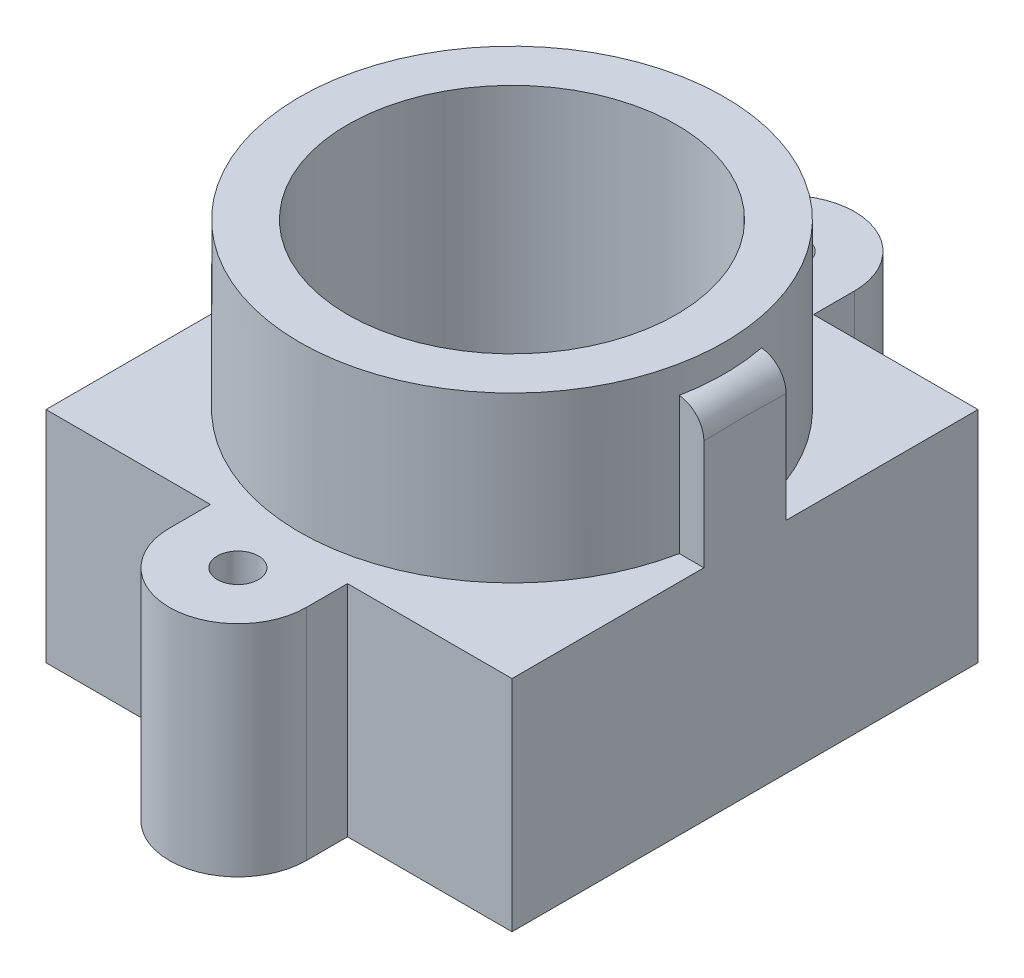
SolidWorks part; units mm, degrees
ref_plane "Front Plane" through (0, 0, 0) normal (0, 0, 1) x (1, 0, 0)
ref_plane "Top Plane" through (0, 0, 0) normal (0, 1, 0) x (1, 0, 0)
ref_plane "Right Plane" through (0, 0, 0) normal (1, 0, 0) x (0, 0, -1)
sketch "Sketch1" plane through (0, 0, 0) normal (0, 1, 0) x (1, 0, 0)
  line L0 (-2.5, 8.5) -> (-2.5, 10)
  line L1 (-8.5, 8.5) -> (-2.5, 8.5)
  line L2 (-8.5, 8.5) -> (-8.5, -8.5)
  line L3 (-8.5, -8.5) -> (-2.5, -8.5)
  line L4 (8.5, 8.5) -> (8.5, -8.5)
  line L5 (-8.5, 8.5) -> (8.5, -8.5) construction
  line L6 (-8.5, -8.5) -> (8.5, 8.5) construction
  line L7 (2.5, 8.5) -> (8.5, 8.5)
  line L8 (2.5, 10) -> (2.5, 8.5)
  line L9 (-2.5, -8.5) -> (-2.5, -10)
  line L10 (2.5, -8.5) -> (8.5, -8.5)
  line L11 (2.5, -10) -> (2.5, -8.5)
  arc A2 (-2.5, 10) -> (2.5, 10) centre (0, 10) cw
  arc A3 (2.5, -10) -> (-2.5, -10) centre (0, -10) cw
  circle A4 centre (0, 10) radius 0.75
  circle A5 centre (0, -10) radius 0.75
  point P0 (0, 0)
  point P14 (0, -12.5)
  point P16 (2.5, 9.25)
  point P22 (0, 12.5)
  dimension "D3" = 5
  dimension "D4" = 25
  dimension "D6" = 1.5
  dimension "D1" = 17
  dimension "D2" = 17
  dimension "D5" = 1.5
extrude "Boss-Extrude1" add sketch "Sketch1" along normal mid plane 8
sketch "Sketch2" plane through (0, 4, 0) normal (0, 1, 0) x (1, 0, 0)
  circle A0 centre (0, 0) radius 7.75
  dimension "D1" = 15.5
extrude "Boss-Extrude2" add sketch "Sketch2" along normal blind 6
sketch "Sketch3" plane through (0, 4, 0) normal (0, 1, 0) x (1, 0, 0)
  line L0 (8.5, 1.5) -> (8.5, -1.5)
  line L1 (8.5, -8.5) -> (8.5, 8.5) construction
  line L2 (8.5, -1.5) -> (7.6035, -1.5)
  line L3 (8.5, 1.5) -> (7.6035, 1.5)
  circle A0 centre (0, 0) radius 7.75 construction
  arc A1 (7.6035, 1.5) -> (7.6035, -1.5) centre (0, 0) cw
  point P4 (8.5, 0)
  dimension "D1" = 3
extrude "Boss-Extrude3" add sketch "Sketch3" along normal blind 5
fillet "Fillet1" radius 1 1 edges at (8.5, 9, 0)
hole_wizard "Tap Drill for M12 Tap1" positions "Sketch4" profile "Sketch5" hole size "M12" standard "ISO" end condition through all
sketch "Sketch4" plane through (0, 10, 0) normal (0, 1, 0) x (1, 0, 0)
  point P0 (0, 0)
sketch "Sketch5" plane through (0, 10, 0) normal (1, 0, 0) x (0, 0, 1)
  line L0 (0, 0) -> (0, 14)
  line L1 (0, 14) -> (6, 14)
  line L2 (6, 14) -> (6, 0)
  line L5 (6, 0) -> (0, 0)
  line L11 (0, -6.35) -> (0, 107.95) construction
  dimension "Thru Hole Dia." = 12
  dimension "Thru Hole Depth" = 14
